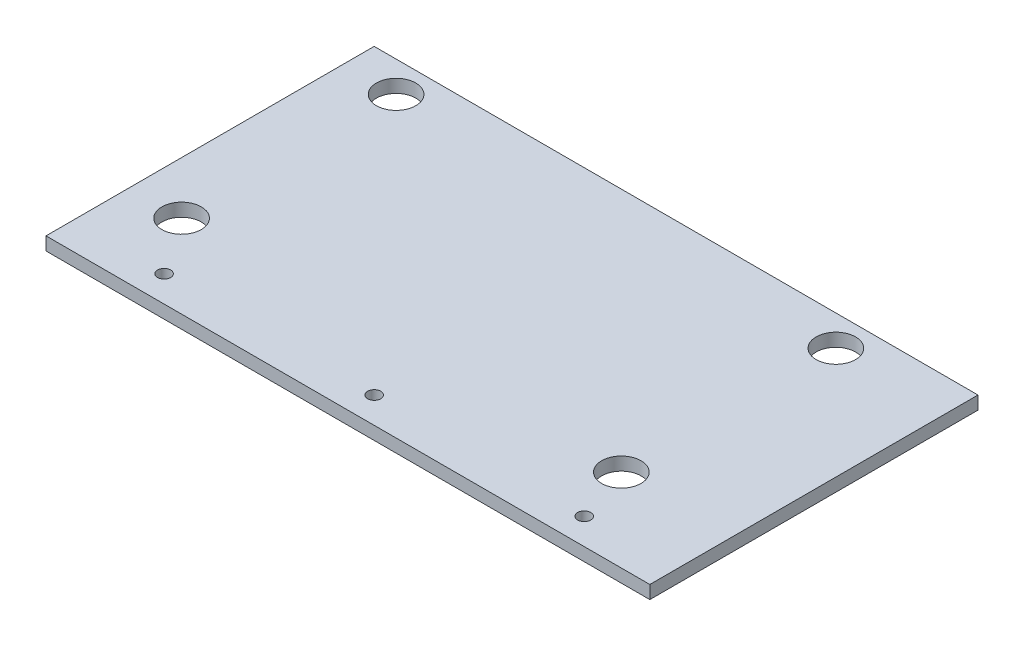
SolidWorks part; units mm, degrees
ref_plane "Front Plane" through (0, 0, 0) normal (0, 0, 1) x (1, 0, 0)
ref_plane "Top Plane" through (0, 0, 0) normal (0, 1, 0) x (1, 0, 0)
ref_plane "Right Plane" through (0, 0, 0) normal (1, 0, 0) x (0, 0, -1)
sketch "Sketch1" plane through (0, 0, 0) normal (0, 1, 0) x (1, 0, 0)
  line L1 (0, 0) -> (292.1, 0)
  line L2 (0, 0) -> (0, 158.75)
  line L3 (0, 158.75) -> (292.1, 158.75)
  line L4 (292.1, 0) -> (292.1, 158.75)
  dimension "D1" = 292.1
  dimension "D2" = 158.75
extrude "Boss-Extrude1" add sketch "Sketch1" along normal blind 6.35
sketch "Sketch2" plane through (0, 6.35, 0) normal (0, 1, 0) x (1, 0, 0)
  line L0 (0, 25.4) -> (292.1, 25.4) construction
  line L1 (0, 12.7) -> (292.1, 12.7) construction
  line L2 (146.05, 0) -> (146.05, 158.75) construction
  line L4 (0, 158.75) -> (0, 0)
  line L5 (0, 0) -> (292.1, 0)
  line L6 (292.1, 0) -> (292.1, 158.75)
  line L7 (292.1, 158.75) -> (0, 158.75)
  line L8 (0, 158.75) -> (0, 0) construction
  line L9 (0, 0) -> (292.1, 0) construction
  line L10 (292.1, 0) -> (292.1, 158.75) construction
  line L11 (292.1, 158.75) -> (0, 158.75) construction
  circle A0 centre (146.05, 12.7) radius 3.175
  circle A1 centre (247.65, 12.7) radius 3.175
  circle A2 centre (44.45, 12.7) radius 3.175
  dimension "D6" = 6.35
  dimension "D7" = 6.35
  dimension "D8" = 6.35
  dimension "D2" = 25.4
  dimension "D3" = 12.7
  dimension "D4" = 101.6
  dimension "D5" = 101.6
extrude "Cut-Extrude2" cut sketch "Sketch2" against normal blind 6.35
sketch "Sketch5" [suppressed] plane through (0, 6.35, 0) normal (0, 1, 0) x (1, 0, 0)
  line L0 (0, 0) -> (292.1, 0) construction
  line L1 (279.4, 31.75) -> (143.9, 31.75) construction
  line L2 (279.4, 31.75) -> (279.4, 75.25) construction
  line L3 (279.4, 75.25) -> (143.9, 75.25) construction
  line L4 (143.9, 31.75) -> (143.9, 75.25) construction
  line L5 (292.1, 0) -> (292.1, 158.75) construction
  circle A0 centre (279.4, 31.75) radius 1.525
  circle A1 centre (279.4, 75.25) radius 1.525
  circle A2 centre (143.9, 75.25) radius 1.525
  circle A3 centre (143.9, 31.75) radius 1.525
  dimension "D3" = 3.05
  dimension "D1" = 43.5
  dimension "D2" = 135.5
  dimension "D4" = 31.75
  dimension "D5" = 12.7
sketch "Sketch6" plane through (0, 6.35, 0) normal (0, 1, 0) x (1, 0, 0)
  line L0 (238.125, 158.75) -> (238.125, 0) construction
  line L1 (292.1, 158.75) -> (0, 158.75) construction
  line L2 (0, 0) -> (292.1, 0) construction
  line L4 (146.05, 158.75) -> (146.05, 0) construction
  line L5 (0, 25.4) -> (292.1, 25.4) construction
  line L6 (0, 158.75) -> (0, 0) construction
  line L7 (292.1, 0) -> (292.1, 158.75) construction
  line L8 (25.4, 40.1879) -> (238.125, 40.1879) construction
  line L9 (25.4, 143.9621) -> (238.125, 143.9621) construction
  line L10 (0, 92.075) -> (292.1, 92.075) construction
  line L11 (0, 158.75) -> (0, 25.4) construction
  line L12 (25.4, 143.9621) -> (25.4, 92.075) construction
  line L13 (25.4, 92.075) -> (25.4, 40.1879) construction
  circle A0 centre (25.4, 40.1879) radius 9.525
  circle A1 centre (238.125, 40.1879) radius 9.525
  circle A2 centre (25.4, 143.9621) radius 9.525
  circle A3 centre (238.125, 143.9621) radius 9.525
  point P6 (0, 0)
  dimension "D2" = 19.05
  dimension "D3" = 19.05
  dimension "D1" = 25.4
  dimension "D4" = 25.4
  dimension "D5" = 53.975
extrude "Cut-Extrude3" cut sketch "Sketch6" against normal through all
sketch "Sketch8" plane through (0, 6.35, 0) normal (0, 1, 0) x (1, 0, 0)
  line L0 (265.43, 121.908) -> (265.43, 112.242) construction
  line L1 (270.764, 112.242) -> (270.764, 121.908) construction
  line L2 (265.43, 96.908) -> (265.43, 87.242)
  line L3 (270.764, 87.242) -> (270.764, 96.908)
  line L4 (265.43, 96.908) -> (265.43, 87.242) construction
  line L5 (270.764, 87.242) -> (270.764, 96.908) construction
  line L6 (265.43, 146.908) -> (265.43, 137.242) construction
  line L7 (270.764, 137.242) -> (270.764, 146.908) construction
  line L8 (265.43, 96.908) -> (265.43, 87.242) construction
  line L9 (270.764, 87.242) -> (270.764, 96.908) construction
  line L10 (265.43, 121.908) -> (265.43, 112.242) construction
  line L11 (270.764, 112.242) -> (270.764, 121.908) construction
  line L12 (265.43, 71.908) -> (265.43, 62.242) construction
  line L13 (270.764, 62.242) -> (270.764, 71.908) construction
  line L14 (265.43, 96.908) -> (265.43, 87.242) construction
  line L15 (270.764, 87.242) -> (270.764, 96.908) construction
  line L16 (265.43, 71.908) -> (265.43, 62.242) construction
  line L17 (270.764, 62.242) -> (270.764, 71.908) construction
  line L18 (265.43, 46.908) -> (265.43, 37.242) construction
  line L19 (270.764, 37.242) -> (270.764, 46.908) construction
  line L20 (265.43, 96.908) -> (265.43, 121.908) construction
  line L21 (268.097, 137.242) -> (268.097, 146.908) construction
  line L22 (268.097, 37.242) -> (268.097, 46.908) construction
  line L23 (150.114, 129.54) -> (140.589, 129.54) construction
  line L24 (140.589, 124.46) -> (150.114, 124.46) construction
  line L25 (213.1283, 38.3159) -> (211.5027, 38.3159)
  line L26 (211.5027, 34.7345) -> (213.1283, 34.7345)
  line L27 (222.285, 31.6611) -> (222.285, 152.4889)
  line L28 (222.285, 152.4889) -> (177.2, 152.4889)
  line L29 (177.2, 152.4889) -> (177.2, 31.6611)
  line L30 (177.2, 31.6611) -> (222.285, 31.6611)
  line L31 (222.285, 31.6611) -> (222.285, 152.4889) construction
  line L32 (222.285, 152.4889) -> (177.2, 152.4889) construction
  line L33 (177.2, 152.4889) -> (177.2, 31.6611) construction
  line L34 (177.2, 31.6611) -> (222.285, 31.6611) construction
  line L35 (213.1283, 38.3159) -> (211.5027, 38.3159)
  line L36 (211.5027, 34.7345) -> (213.1283, 34.7345)
  line L37 (187.9823, 38.3159) -> (186.3567, 38.3159)
  line L38 (186.3567, 34.7345) -> (187.9823, 34.7345)
  line L39 (187.9823, 38.3159) -> (186.3567, 38.3159)
  line L40 (186.3567, 34.7345) -> (187.9823, 34.7345)
  line L41 (211.5027, 145.8341) -> (213.1283, 145.8341)
  line L42 (213.1283, 149.4155) -> (211.5027, 149.4155)
  line L43 (211.5027, 145.8341) -> (213.1283, 145.8341)
  line L44 (213.1283, 149.4155) -> (211.5027, 149.4155)
  line L45 (186.3567, 145.8341) -> (187.9823, 145.8341)
  line L46 (187.9823, 149.4155) -> (186.3567, 149.4155)
  line L47 (186.3567, 145.8341) -> (187.9823, 145.8341)
  line L48 (187.9823, 149.4155) -> (186.3567, 149.4155)
  line L49 (200.914, 129.54) -> (191.389, 129.54)
  line L50 (191.389, 124.46) -> (200.914, 124.46)
  line L51 (200.914, 129.54) -> (191.389, 129.54) construction
  line L52 (191.389, 124.46) -> (200.914, 124.46) construction
  line L53 (99.314, 129.54) -> (89.789, 129.54) construction
  line L54 (89.789, 124.46) -> (99.314, 124.46) construction
  line L55 (200.914, 129.54) -> (150.114, 129.54) construction
  line L56 (89.789, 127) -> (200.914, 127) construction
  line L57 (196.1515, 124.46) -> (196.1515, 129.54) construction
  line L58 (94.5515, 124.46) -> (94.5515, 129.54) construction
  line L63 (109.05, 54.7) -> (183.05, 54.7)
  line L64 (183.05, 54.7) -> (183.05, 97.7)
  line L65 (183.05, 97.7) -> (109.05, 97.7)
  line L66 (109.05, 97.7) -> (109.05, 54.7)
  line L67 (109.05, 54.7) -> (183.05, 54.7) construction
  line L68 (183.05, 54.7) -> (183.05, 97.7) construction
  line L69 (183.05, 97.7) -> (109.05, 97.7) construction
  line L70 (109.05, 97.7) -> (109.05, 54.7) construction
  arc A0 (265.43, 112.242) -> (270.764, 112.242) centre (268.097, 112.242) ccw construction
  arc A1 (270.764, 121.908) -> (265.43, 121.908) centre (268.097, 121.908) ccw construction
  arc A2 (265.43, 87.242) -> (270.764, 87.242) centre (268.097, 87.242) ccw
  arc A3 (270.764, 96.908) -> (265.43, 96.908) centre (268.097, 96.908) ccw
  arc A4 (265.43, 87.242) -> (270.764, 87.242) centre (268.097, 87.242) ccw construction
  arc A5 (270.764, 96.908) -> (265.43, 96.908) centre (268.097, 96.908) ccw construction
  arc A6 (265.43, 137.242) -> (270.764, 137.242) centre (268.097, 137.242) ccw construction
  arc A7 (270.764, 146.908) -> (265.43, 146.908) centre (268.097, 146.908) ccw construction
  arc A8 (265.43, 87.242) -> (270.764, 87.242) centre (268.097, 87.242) ccw construction
  arc A9 (270.764, 96.908) -> (265.43, 96.908) centre (268.097, 96.908) ccw construction
  arc A10 (265.43, 112.242) -> (270.764, 112.242) centre (268.097, 112.242) ccw construction
  arc A11 (270.764, 121.908) -> (265.43, 121.908) centre (268.097, 121.908) ccw construction
  arc A12 (265.43, 62.242) -> (270.764, 62.242) centre (268.097, 62.242) ccw construction
  arc A13 (270.764, 71.908) -> (265.43, 71.908) centre (268.097, 71.908) ccw construction
  arc A14 (265.43, 87.242) -> (270.764, 87.242) centre (268.097, 87.242) ccw construction
  arc A15 (270.764, 96.908) -> (265.43, 96.908) centre (268.097, 96.908) ccw construction
  arc A16 (265.43, 62.242) -> (270.764, 62.242) centre (268.097, 62.242) ccw construction
  arc A17 (270.764, 71.908) -> (265.43, 71.908) centre (268.097, 71.908) ccw construction
  arc A18 (265.43, 37.242) -> (270.764, 37.242) centre (268.097, 37.242) ccw construction
  arc A19 (270.764, 46.908) -> (265.43, 46.908) centre (268.097, 46.908) ccw construction
  circle A20 centre (268.097, 42.075) radius 2.667
  circle A21 centre (268.097, 142.075) radius 2.667
  arc A22 (140.589, 129.54) -> (140.589, 124.46) centre (140.589, 127) ccw construction
  arc A23 (150.114, 124.46) -> (150.114, 129.54) centre (150.114, 127) ccw construction
  arc A24 (211.5027, 38.3159) -> (211.5027, 34.7345) centre (211.5027, 36.5252) ccw
  arc A25 (213.1283, 34.7345) -> (213.1283, 38.3159) centre (213.1283, 36.5252) ccw
  arc A26 (211.5027, 38.3159) -> (211.5027, 34.7345) centre (211.5027, 36.5252) ccw
  arc A27 (213.1283, 34.7345) -> (213.1283, 38.3159) centre (213.1283, 36.5252) ccw
  arc A28 (187.9823, 34.7345) -> (187.9823, 38.3159) centre (187.9823, 36.5252) ccw
  arc A29 (186.3567, 38.3159) -> (186.3567, 34.7345) centre (186.3567, 36.5252) ccw
  arc A30 (187.9823, 34.7345) -> (187.9823, 38.3159) centre (187.9823, 36.5252) ccw
  arc A31 (186.3567, 38.3159) -> (186.3567, 34.7345) centre (186.3567, 36.5252) ccw
  arc A32 (211.5027, 149.4155) -> (211.5027, 145.8341) centre (211.5027, 147.6248) ccw
  arc A33 (213.1283, 145.8341) -> (213.1283, 149.4155) centre (213.1283, 147.6248) ccw
  arc A34 (211.5027, 149.4155) -> (211.5027, 145.8341) centre (211.5027, 147.6248) ccw
  arc A35 (213.1283, 145.8341) -> (213.1283, 149.4155) centre (213.1283, 147.6248) ccw
  arc A36 (187.9823, 145.8341) -> (187.9823, 149.4155) centre (187.9823, 147.6248) ccw
  arc A37 (186.3567, 149.4155) -> (186.3567, 145.8341) centre (186.3567, 147.6248) ccw
  arc A38 (187.9823, 145.8341) -> (187.9823, 149.4155) centre (187.9823, 147.6248) ccw
  arc A39 (186.3567, 149.4155) -> (186.3567, 145.8341) centre (186.3567, 147.6248) ccw
  arc A40 (191.389, 129.54) -> (191.389, 124.46) centre (191.389, 127) ccw
  arc A41 (200.914, 124.46) -> (200.914, 129.54) centre (200.914, 127) ccw
  arc A42 (191.389, 129.54) -> (191.389, 124.46) centre (191.389, 127) ccw construction
  arc A43 (200.914, 124.46) -> (200.914, 129.54) centre (200.914, 127) ccw construction
  arc A44 (89.789, 129.54) -> (89.789, 124.46) centre (89.789, 127) ccw construction
  arc A45 (99.314, 124.46) -> (99.314, 129.54) centre (99.314, 127) ccw construction
  circle A46 centre (196.1515, 127) radius 2.54
  circle A47 centre (145.3515, 127) radius 2.54
  circle A48 centre (94.5515, 127) radius 2.54
  circle A50 centre (111.2, 57.2) radius 1.5
  circle A51 centre (111.2, 57.2) radius 1.5
  circle A52 centre (180.9, 57.2) radius 1.5
  circle A53 centre (180.9, 57.2) radius 1.5
  circle A54 centre (180.9, 95.2) radius 1.5
  circle A55 centre (180.9, 95.2) radius 1.5
  circle A56 centre (111.2, 95.2) radius 1.5
  circle A57 centre (111.2, 95.2) radius 1.5
  circle A58 centre (111.125, 7.62) radius 1.5875
  circle A59 centre (111.125, 7.62) radius 1.5875
  circle A60 centre (180.975, 7.62) radius 1.5875
  circle A61 centre (180.975, 7.62) radius 1.5875
  circle A62 centre (180.975, 44.45) radius 1.5875
  circle A63 centre (180.975, 44.45) radius 1.5875
  circle A64 centre (111.125, 44.45) radius 1.5875
  circle A65 centre (111.125, 44.45) radius 1.5875
  circle A66 centre (7.62, 123.825) radius 1.5875
  circle A67 centre (7.62, 123.825) radius 1.5875
  circle A68 centre (7.62, 60.325) radius 1.5875
  circle A69 centre (7.62, 60.325) radius 1.5875
  circle A70 centre (44.45, 60.325) radius 1.5875
  circle A71 centre (44.45, 60.325) radius 1.5875
  circle A72 centre (44.45, 123.825) radius 1.5875
  circle A73 centre (44.45, 123.825) radius 1.5875
  circle A74 centre (93.326, 36.5125) radius 2.0955
  circle A75 centre (93.326, 36.5125) radius 2.0955
  circle A77 centre (151.8, 132.099) radius 2.0955
  circle A78 centre (151.8, 132.099) radius 2.0955
  circle A80 centre (198.774, 36.5125) radius 2.0955
  circle A81 centre (198.774, 36.5125) radius 2.0955
  circle A83 centre (151.8, 52.051) radius 2.0955
  circle A84 centre (151.8, 52.051) radius 2.0955
  circle A86 centre (259.099, 92.075) radius 2.0955
  circle A87 centre (259.099, 92.075) radius 2.0955
  point P118 (0, 0)
  point P119 (196.1515, 127)
  point P120 (0, 0)
  dimension "D4" = 25
  dimension "D12" = 50.8
  dimension "D1" = 0
  dimension "D5" = 0
  dimension "D6" = 0
  dimension "D7" = 0
  dimension "D8" = 0
  dimension "D9" = 0
  dimension "D10" = 0
  dimension "D13" = 0
  dimension "D14" = 0
  dimension "D15" = 0
  dimension "D16" = 0
  dimension "D17" = 0
  dimension "D18" = 0
  dimension "D19" = 0
  dimension "D20" = 0
  dimension "D21" = 0
  dimension "D22" = 0
  dimension "D23" = 0
  dimension "D24" = 0
  dimension "D25" = 0
  dimension "D26" = 0
  dimension "D27" = 0
  dimension "D28" = 0
  dimension "D29" = 0
  dimension "D30" = 0
  dimension "D2" = 3
  dimension "D3" = 3
  dimension "D11" = 3
equation "\"D5@Sketch2\"=\"D4@Sketch2\""
equation "\"D7@Sketch2\"=\"D6@Sketch2\""
equation "\"D8@Sketch2\"=\"D7@Sketch2\""
equation "\"D4@Sketch5\"=1.25*25.4"
